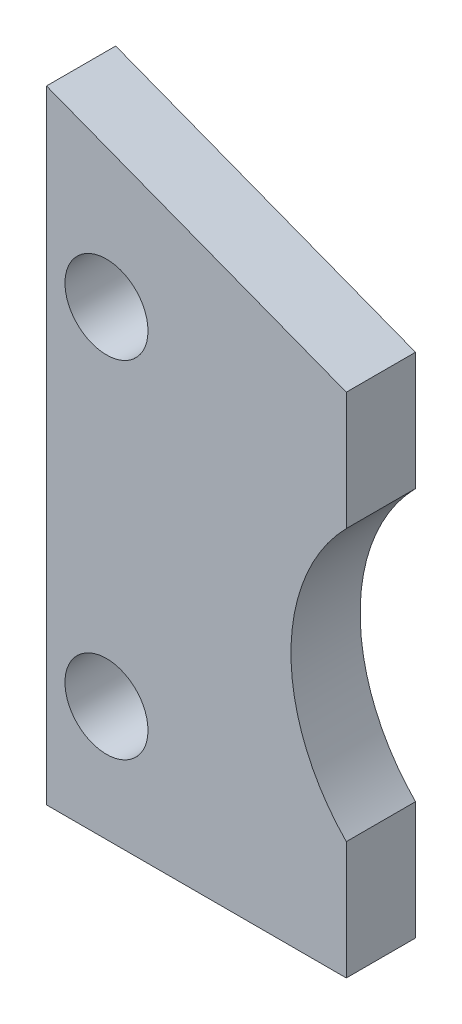
SolidWorks part; units mm, degrees
ref_plane "Ön Düzlem" through (0, 0, 0) normal (0, 0, 1) x (1, 0, 0)
ref_plane "Üst Düzlem" through (0, 0, 0) normal (0, 1, 0) x (1, 0, 0)
ref_plane "Sağ Düzlem" through (0, 0, 0) normal (1, 0, 0) x (0, 0, -1)
sketch "Çizim1" plane through (0, 0, 0) normal (0, 0, 1) x (1, 0, 0)
  line L0 (0, 0) -> (65, 0)
  line L1 (65, 0) -> (65, 25.6061)
  line L2 (65, 110) -> (0, 135)
  line L3 (0, 135) -> (0, 0)
  line L4 (65, 84.3939) -> (65, 110)
  arc A0 (65, 84.3939) -> (65, 25.6061) centre (95, 55) ccw
  dimension "D4" = 42
  dimension "D1" = 135
  dimension "D2" = 65
  dimension "D3" = 110
  dimension "D5" = 95
  dimension "D6" = 55
base flange "Taban-Flanş1" sketch "Çizim1" thickness 15 reverse thickness direction no parameters "D1"=0.7366
sketch "Çizim2" plane through (0, 0, 0) normal (0, 0, 1) x (1, 0, 0)
  line L0 (0, 135) -> (0, 0) construction
  circle A0 centre (13, 100) radius 9
  circle A1 centre (13, 25) radius 9
  point P6 (0, 0)
  point P9 (0, 0)
  dimension "D1" = 75
  dimension "D3" = 18
  dimension "D2" = 13
  dimension "D4" = 35
extrude "Kes-Ekstrüzyon1" cut sketch "Çizim2" against normal through all normal cut yes
sketch "Çizim3" plane through (0, 0, 0) normal (0, 0, -1) x (-1, 0, 0)
  line L0 (0, 0) -> (-65, 0) construction
  line L2 (-65, 84.3939) -> (-65, 110) construction
  line L5 (0, 135) -> (0, 0) construction
  circle A0 centre (-13, 100) radius 9
  circle A1 centre (-13, 25) radius 9
  dimension "D1" = 18
  dimension "D2" = 75
  dimension "D3" = 25
  dimension "D4" = 52
  dimension "D5" = 13
sketch "Büküm-Çizgileri1" [suppressed] plane through (0, 0, 0) normal (0, 1, 0) x (1, 0, 0)
sketch "Sınırlandırma-Kutusu1" [suppressed] plane through (0, 0, 0) normal (0, 1, 0) x (1, 0, 0)
sheet metal parameters "Sac-Levha1" thickness 15 parameters "D1"=0.7366
flat pattern "Düz-Çoğaltma1" [suppressed]
sketch "Büküm-Çizgileri2" plane through (0, 0, 0) normal (0, 1, 0) x (1, 0, 0)
sketch3d "Sınırlandırma-Kutusu2" [suppressed]
  line L0 (30, 80, 0) -> (30, -55, 0) construction
  line L1 (95, 80, 0) -> (95, -55, 0) construction
  line L2 (30, 80, 0) -> (95, 80, 0) construction
  line L3 (30, -55, 0) -> (95, -55, 0) construction
sheet metal parameters "Sac-Levha2" thickness 15 parameters "D1"=0.7366
flat pattern "Düz-Çoğaltma1"
sketch "Büküm-Çizgileri2" plane through (0, 0, 0) normal (0, 1, 0) x (1, 0, 0)
sketch3d "Sınırlandırma-Kutusu2" [suppressed]
  line L0 (-30, 80, 0) -> (-30, -55, 0) construction
  line L1 (-95, 80, 0) -> (-95, -55, 0) construction
  line L2 (-30, 80, 0) -> (-95, 80, 0) construction
  line L3 (-30, -55, 0) -> (-95, -55, 0) construction
